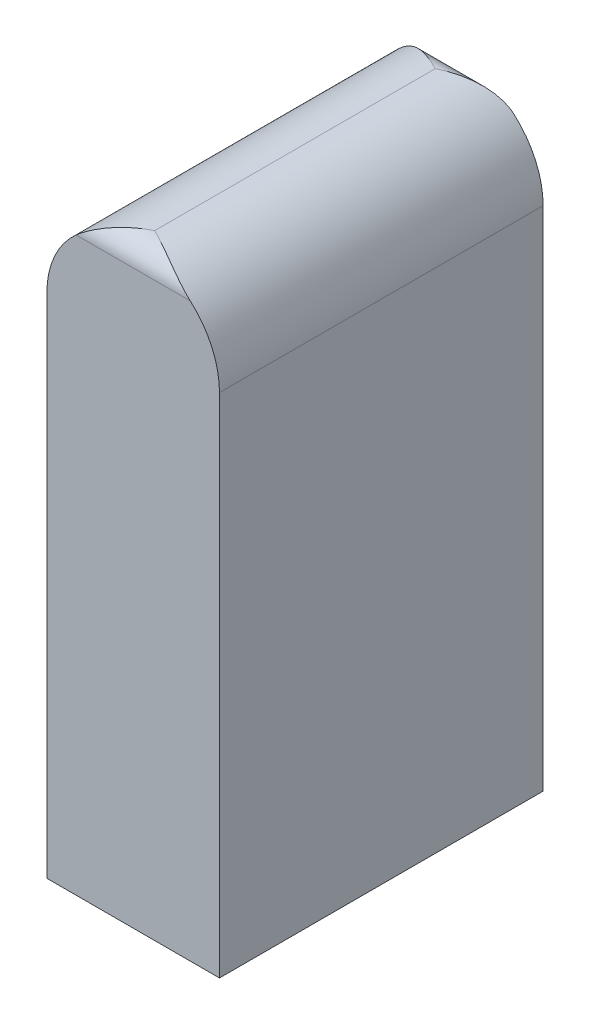
SolidWorks part; units mm, degrees
ref_plane "Front Plane" through (0, 0, 0) normal (1, 0, 0) x (0, 1, 0)
ref_plane "Top Plane" through (0, 0, 0) normal (0, 0, 1) x (0, 1, 0)
ref_plane "Right Plane" through (0, 0, 0) normal (0, 1, 0) x (-1, 0, 0)
sketch "Sketch1" plane through (0, 0, 0) normal (1, 0, 0) x (0, 1, 0)
  line L1 (-27.5, -15) -> (25.5, -15)
  line L2 (-27.5, -15) -> (-27.5, 15)
  line L3 (-27.5, 15) -> (25.5, 15)
  line L4 (27.5, -13) -> (27.5, 13)
  line L5 (-27.5, -15) -> (27.5, 15) construction
  line L6 (-27.5, 15) -> (27.5, -15) construction
  arc A0 (27.5, -13) -> (25.5, -15) centre (25.5, -13) cw
  arc A1 (27.5, 13) -> (25.5, 15) centre (25.5, 13) ccw
  point P0 (0, 0)
  dimension "D3" = 2
  dimension "D1" = 55
  dimension "D2" = 30
extrude "Boss-Extrude1" add sketch "Sketch1" along normal blind 16
fillet "Fillet6" radius 8 3 edges at (16, 26.9142, -14.4142) (16, 27.5, 0) (16, 26.9142, 14.4142)
fillet "Fillet7" radius 8 5 edges at (4, 27.5, 13) (4, 27.5, -13) (0, 26.9142, 14.4142) (0, 27.5, 0) (0, 26.9142, -14.4142)
